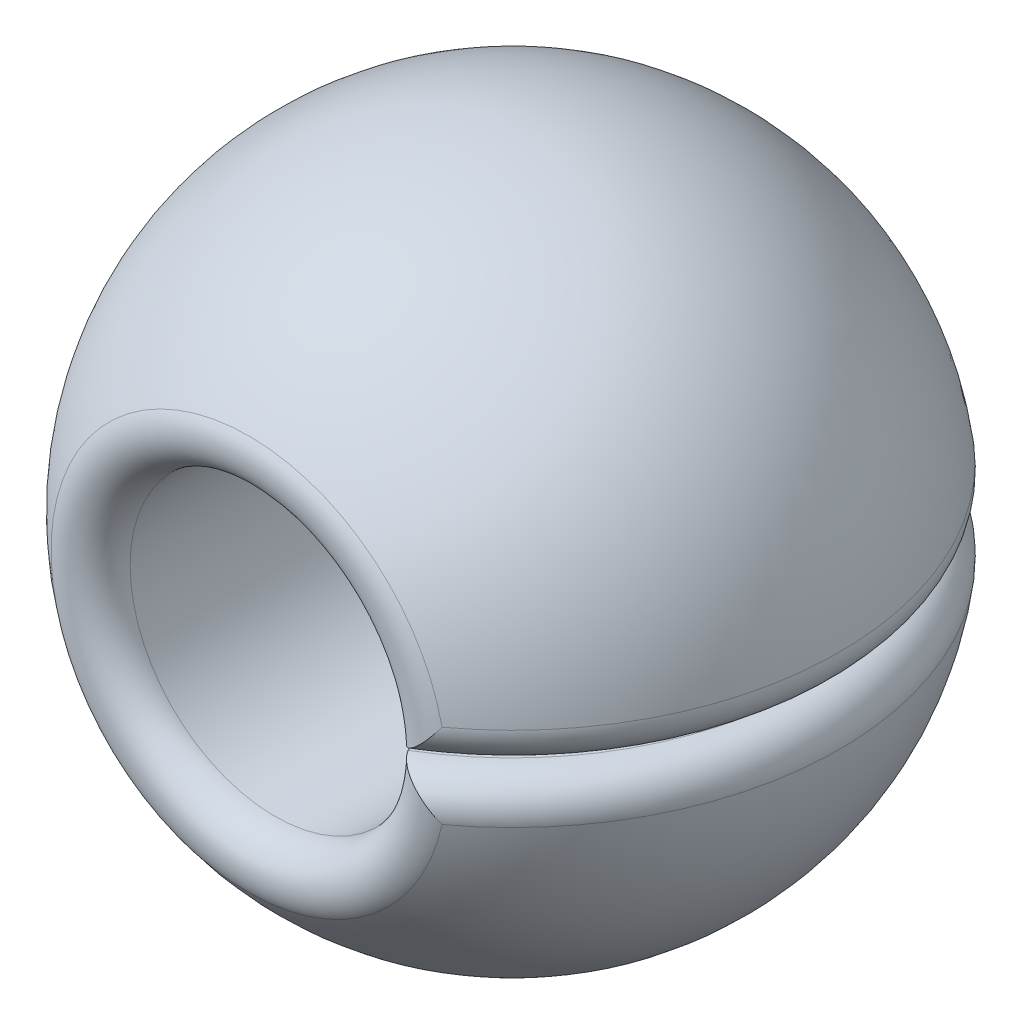
SolidWorks part; units mm, degrees
ref_plane "정면" through (0, 0, 0) normal (0, 0, 1) x (1, 0, 0)
ref_plane "윗면" through (0, 0, 0) normal (0, 1, 0) x (1, 0, 0)
ref_plane "우측면" through (0, 0, 0) normal (1, 0, 0) x (0, 0, -1)
sketch "스케치1" plane through (0, 0, 0) normal (0, 0, 1) x (1, 0, 0)
  line L0 (0, 11.7897) -> (0, -13.2661) construction
  line L1 (0, 10) -> (0, -10)
  arc A0 (0, 10) -> (0, -10) centre (0, 0) ccw
  dimension "D1" = 20
revolve "회전2" add sketch "스케치1" angle 360 about L0
sketch "스케치2" plane through (0, 0, 0) normal (0, 0, 1) x (1, 0, 0)
  circle A1 centre (0, 0) radius 4.4
  dimension "D1" = 8.8
extrude "컷-돌출1" cut sketch "스케치2" against normal mid plane 30 contours A1
sketch "스케치3" plane through (0, 0, 0) normal (0, 0, 1) x (1, 0, 0)
  line L1 (1.4366, 0.15) -> (11.8583, 0.15)
  line L2 (1.4366, 0.15) -> (1.4366, -0.15)
  line L3 (1.4366, -0.15) -> (11.8583, -0.15)
  line L4 (11.8583, 0.15) -> (11.8583, -0.15)
  point P4 (1.4366, 0)
  dimension "D1" = 0.3
extrude "컷-돌출2" cut sketch "스케치3" against normal mid plane 30
fillet "필렛1" radius 1 4 edges at (-4.4, 0, 8.98) (9.9989, -0.15, 0) (-4.4, 0, -8.98) (9.9989, 0.15, 0)
ref_point "점1"
